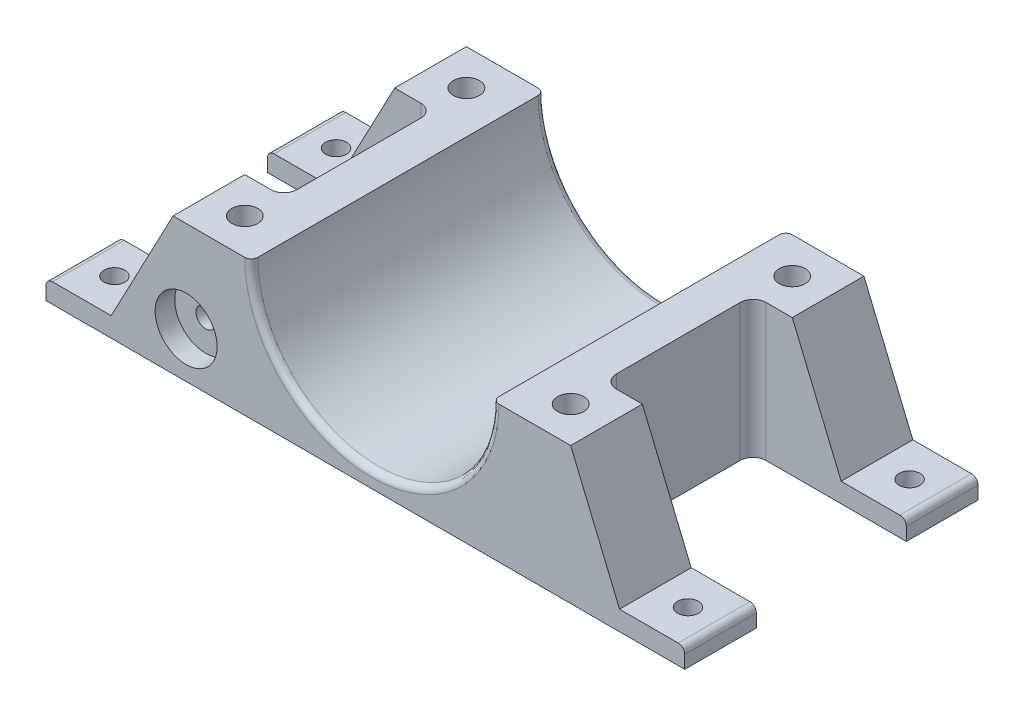
SolidWorks part; units mm, degrees
ref_plane "Front Plane" through (0, 0, 0) normal (0, 0, 1) x (1, 0, 0)
ref_plane "Top Plane" through (0, 0, 0) normal (0, 1, 0) x (1, 0, 0)
ref_plane "Right Plane" through (0, 0, 0) normal (1, 0, 0) x (0, 0, -1)
sketch "Sketch1" plane through (0, 0, 0) normal (0, 0, 1) x (1, 0, 0)
  line L0 (0, 0) -> (50000, 0) construction
  line L1 (0, 0) -> (0, 50000) construction
  line L2 (-18.5, 0) -> (-30.5, 0)
  line L3 (-30.5, 0) -> (-40, -18)
  line L4 (-40, -18) -> (-50, -18)
  line L5 (-50, -18) -> (-50, -21)
  line L6 (-50, -21) -> (0, -21)
  line L7 (0, -18.5) -> (50000, -18.5) construction
  line L8 (18.5, 0) -> (30.5, 0)
  line L9 (30.5, 0) -> (38, -18)
  line L10 (38, -18) -> (48, -18)
  line L11 (48, -18) -> (48, -21)
  line L12 (48, -21) -> (0, -21)
  circle A0 centre (0, 0) radius 18 construction
  arc A1 (-18.5, 0) -> (18.5, 0) centre (0, 0) ccw
  point P16 (0, -18.5)
  dimension "D1" = 36
  dimension "D2" = 0.5
  dimension "D3" = 12
  dimension "D4" = 10
  dimension "D5" = 2.5
  dimension "D6" = 18
  dimension "D7" = 50
  dimension "D8" = 10
  dimension "D9" = 12
  dimension "50" = 48
  dimension "D10" = 18
extrude "Boss-Extrude1" add sketch "Sketch1" along normal mid plane 45
sketch "Sketch2" plane through (0, 0, 0) normal (0, 1, 0) x (1, 0, 0)
  line L0 (-65, 0) -> (-50065, 0) construction
  line L1 (-50, -22.5) -> (-50, 22.5) construction
  line L2 (-24.5, -11.5) -> (-24.5, 11.5)
  line L3 (-30.5, -22.5) -> (-30.5, 22.5) construction
  line L4 (-50, -11.5) -> (-50, 11.5)
  line L5 (-24.5, 11.5) -> (-50, 11.5)
  line L6 (-40, 22.5) -> (-50, 22.5) construction
  line L7 (-24.5, -11.5) -> (-50, -11.5)
  line L8 (48, -22.5) -> (48, 22.5) construction
  line L9 (48, -11.5) -> (48, 11.5)
  line L10 (48, -11.5) -> (48, 11.5)
  line L11 (48, 11.5) -> (24.5, 11.5)
  line L13 (24.5, 11.5) -> (24.5, -11.5)
  line L14 (48, -11.5) -> (24.5, -11.5)
  line L15 (48, 22.5) -> (38, 22.5) construction
  line L16 (-18.5, -22.5) -> (-18.5, 22.5) construction
  line L19 (18.5, -22.5) -> (18.5, 22.5) construction
  point P4 (-50, 0)
  point P10 (-30.5, 0)
  point P15 (-50, 0)
  point P24 (24.5, 0)
  point P25 (48, 0)
  line M8 (-30.5, 22.5) -> (-30.5, -22.5)
  dimension "D1" = 11
  dimension "D2" = 11
  dimension "D3" = 6
  dimension "D4" = 6
extrude "Cut-Extrude1" cut sketch "Sketch2" against normal blind 65 contours L2 L0 L4 L7 | L0 L5 L4 M8 | L0 L10 L11 L13 | L9 L0 L13 L14 | L7 L4 L5 L2 | L13 L14 L10 L11 region at (-40.25, 0, 0) region at (36.25, 0, 0)
sketch "Sketch3" plane through (0, -18, 0) normal (0, 1, 0) x (1, 0, 0)
  line L0 (-60, 17) -> (-50060, 17) construction
  line L1 (-50, 11.5) -> (-50, 22.5) construction
  line L2 (-45, 22.5) -> (-45, 50022.5) construction
  line L3 (-40, 22.5) -> (-50, 22.5) construction
  line L4 (0, 0) -> (50000, 0) construction
  line L5 (43, 22.5) -> (43, 50022.5) construction
  line L6 (48, 22.5) -> (38, 22.5) construction
  circle A0 centre (-45, 17) radius 1.6
  circle A1 centre (43, 17) radius 1.6
  circle A2 centre (43, -17) radius 1.6
  circle A3 centre (-45, -17) radius 1.6
  point P4 (-50, 17)
  point P9 (-45, 22.5)
  point P17 (43, 22.5)
  dimension "D1" = 3.2
  dimension "D2" = 3.2
  dimension "D3" = 88
  dimension "D4" = 34
extrude "Cut-Extrude2" cut sketch "Sketch3" against normal blind 65
sketch "Sketch4" plane through (0, 0, 22.5) normal (0, 0, 1) x (1, 0, 0)
  line L0 (-50, -21) -> (48, -21) construction
  circle A0 centre (-28.5, -14) radius 4.75
  dimension "D2" = 9.5
  dimension "D1" = 10
  dimension "D3" = 7
extrude "Bearing-Hole" cut sketch "Sketch4" against normal blind 3
mirror "Mirror1" about plane through (0, 0, 0) normal (0, 0, 1) of "Bearing-Hole"
sketch "Sketch5" plane through (0, 0, 19.5) normal (0, 0, 1) x (1, 0, 0)
  line L0 (-28.5, -9.3202) -> (-28.5, 49990.6798) construction
  line L1 (-31.3186, -14) -> (49968.6814, -14) construction
  line L2 (-23.75, -14) -> (-33.25, -14) construction
  line L3 (-33.25, -8.25) -> (-33.25, 49991.75) construction
  line L4 (-35.25, -9.25) -> (49964.75, -9.25) construction
  circle A0 centre (-28.5, -14) radius 1.5
  circle A1 centre (-28.5, -14) radius 4.75 construction
  circle A2 centre (-28.5, -14) radius 4.75 construction
  point P17 (-28.5, -9.25)
  point P18 (0, 0)
  dimension "D1" = 3
extrude "Cut-Extrude4" cut sketch "Sketch5" against normal through all both and the other way through all
fillet "Fillet2" radius 1 6 edges at (0, -18.5, -22.5) (0, -18.5, 22.5) (48, -18, -17) (48, -18, 17) (-50, -18, -17) (-50, -18, 17)
fillet "Fillet3" radius 2 4 edges at (24.5, -10.5, -11.5) (24.5, -10.5, 11.5) (-24.5, -10.5, 11.5) (-24.5, -10.5, -11.5)
sketch "Sketch6" plane through (0, 0, 0) normal (0, 1, 0) x (1, 0, 0)
  line L0 (-25, 22.5) -> (-25, -49977.5) construction
  line L1 (-19.5, 22.5) -> (-30.5, 22.5) construction
  line L2 (0, 0) -> (0, -50000) construction
  line L3 (-34.6439, 17) -> (-50.1387, 17) construction
  line L5 (0, 0) -> (50000, 0) construction
  circle A0 centre (-25, 17) radius 2
  circle A1 centre (25, 17) radius 2
  circle A2 centre (25, -17) radius 2
  circle A3 centre (-25, -17) radius 2
  point P4 (-25, 22.5)
  dimension "D1" = 4
extrude "Cut-Extrude5" cut sketch "Sketch6" against normal blind 10 and the other way through all
